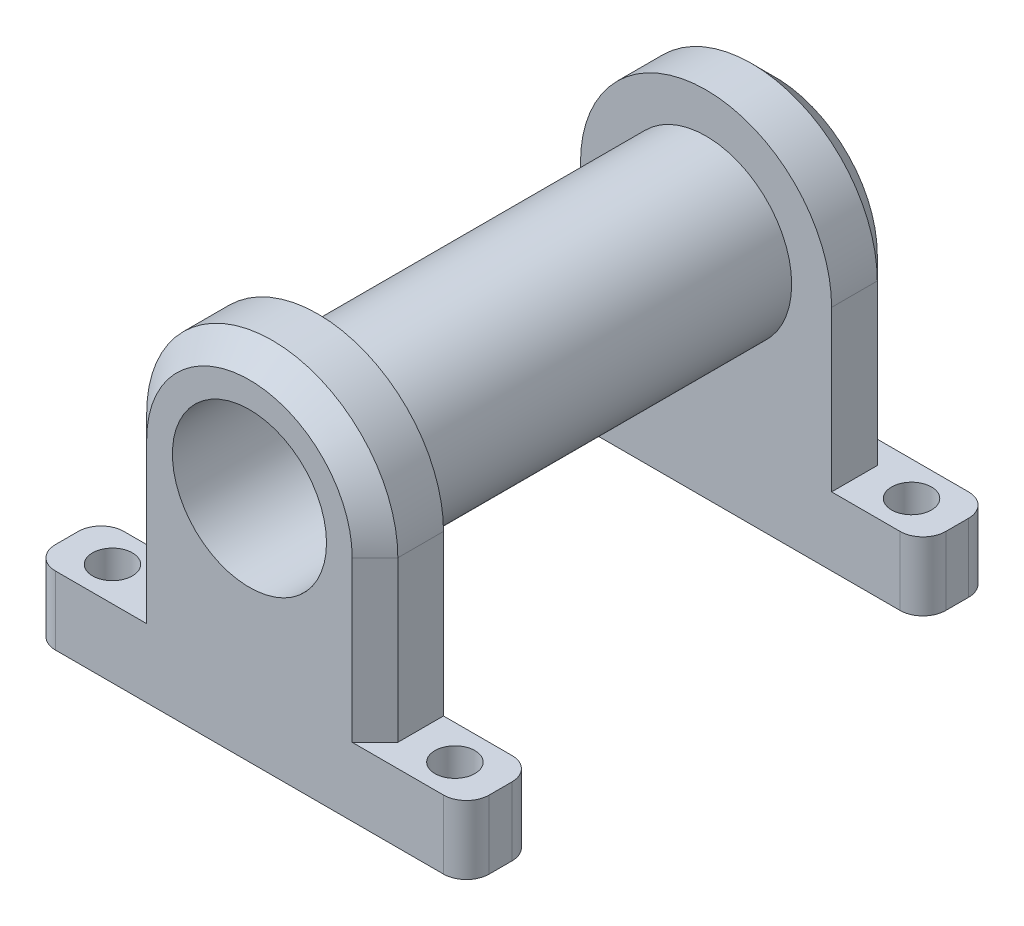
SolidWorks part; units mm, degrees
ref_plane "Front Plane" through (0, 0, 0) normal (0, 0, 1) x (1, 0, 0)
ref_plane "Top Plane" through (0, 0, 0) normal (0, 1, 0) x (1, 0, 0)
ref_plane "Right Plane" through (0, 0, 0) normal (1, 0, 0) x (0, 0, -1)
sketch "Sketch1" plane through (0, 0, 0) normal (0, 0, 1) x (1, 0, 0)
  line L0 (-11, 0) -> (-11, -14)
  line L1 (-11, -20) -> (11, -20)
  line L2 (11, -14) -> (11, 0)
  line L3 (-11, -14) -> (11, -14) construction
  line L4 (-11, -20) -> (-19, -20)
  line L6 (-11, -14) -> (-19, -14)
  line L7 (-19, -20) -> (-19, -14)
  line L8 (11, -20) -> (19, -20)
  line L10 (11, -14) -> (19, -14)
  line L11 (19, -20) -> (19, -14)
  arc A0 (11, 0) -> (-11, 0) centre (0, 0) ccw
  dimension "D1" = 22
  dimension "D2" = 20
  dimension "D3" = 8
  dimension "D4" = 6
extrude "Boss-Extrude1" add sketch "Sketch1" along normal blind 6
sketch "Sketch2" plane through (0, 0, 6) normal (0, 0, 1) x (1, 0, 0)
  circle A0 centre (0, 0) radius 7.5
  dimension "D1" = 15
extrude "Boss-Extrude2" add sketch "Sketch2" along normal blind 34
sketch "Sketch3" plane through (0, 0, 40) normal (0, 0, 1) x (1, 0, 0)
  line L3 (-11, 0) -> (-11, -14)
  line L4 (-19, -20) -> (19, -20)
  line L5 (11, -14) -> (11, 0)
  line L6 (-11, 0) -> (-11, -14)
  line L7 (-19, -20) -> (19, -20)
  line L8 (11, -14) -> (11, 0)
  line L13 (-19, -14) -> (-19, -20)
  line L14 (-19, -14) -> (-19, -20)
  line L15 (19, -20) -> (19, -14)
  line L16 (19, -20) -> (19, -14)
  line L17 (19, -14) -> (11, -14)
  line L18 (19, -14) -> (11, -14)
  line L19 (-11, -14) -> (-19, -14)
  line L20 (-11, -14) -> (-19, -14)
  arc A2 (11, 0) -> (-11, 0) centre (0, 0) ccw
  arc A3 (11, 0) -> (-11, 0) centre (0, 0) ccw
  dimension "D1" = 0
extrude "Boss-Extrude3" add sketch "Sketch3" along normal blind 6
sketch "Sketch4" plane through (0, 0, 46) normal (0, 0, 1) x (1, 0, 0)
  circle A0 centre (0, 0) radius 6.75
  dimension "D1" = 13.5
extrude "Cut-Extrude1" cut sketch "Sketch4" against normal through all
sketch "Sketch5" plane through (0, -20, 0) normal (0, -1, 0) x (1, 0, 0)
  line L0 (-5, 43) -> (-11, 43) construction
  line L1 (-5, 43) -> (5, 43) construction
  line L2 (-5, 43) -> (-5, 3) construction
  line L3 (-5, 3) -> (5, 3) construction
  line L4 (5, 43) -> (5, 3) construction
  line L5 (-11, 46) -> (-11, 40) construction
  line L6 (-5, 3) -> (-11, 3) construction
  line L7 (-11, 6) -> (-11, 0) construction
  line L8 (0, 3) -> (0, 0) construction
  circle A0 centre (-5, 43) radius 2.25
  circle A1 centre (5, 43) radius 2.25
  circle A2 centre (-5, 3) radius 2.25
  circle A3 centre (5, 3) radius 2.25
  dimension "D3" = 4.5
  dimension "D1" = 10
  dimension "D2" = 40
extrude "Cut-Extrude2" cut sketch "Sketch5" against normal blind 13
sketch "Sketch9" plane through (0, -14, 0) normal (0, 1, 0) x (1, 0, 0)
  line L0 (-15, -3) -> (15, -3) construction
  line L1 (15, -3) -> (15, -43) construction
  line L2 (15, -43) -> (-15, -43) construction
  line L3 (-15, -43) -> (-15, -3) construction
  line L4 (0, 0) -> (0, -3) construction
  line L5 (0, -3) -> (0, -43) construction
  line L6 (11, 0) -> (-11, 0) construction
  line L7 (-11, -46) -> (-19, -46) construction
  circle A0 centre (15, -43) radius 1.75
  circle A1 centre (-15, -43) radius 1.75
  circle A2 centre (15, -3) radius 1.75
  circle A3 centre (-15, -3) radius 1.75
  point P11 (9.8525, -3.5184)
  dimension "D4" = 3.5
  dimension "D1" = 30
  dimension "D2" = 3
  dimension "D3" = 3
extrude "Cut-Extrude5" cut sketch "Sketch9" against normal through all
fillet "Fillet1" radius 2 8 edges at (-19, -17, 0) (-19, -17, 40) (-19, -17, 6) (-19, -17, 46) (19, -17, 46) (19, -17, 40) (19, -17, 6) (19, -17, 0)
chamfer "Chamfer4" distance 2 angle 45 6 edges at (11, -7, 0) (-11, -7, 0) (0, 11, 0) (11, -7, 46) (0, 11, 46) (-11, -7, 46)
